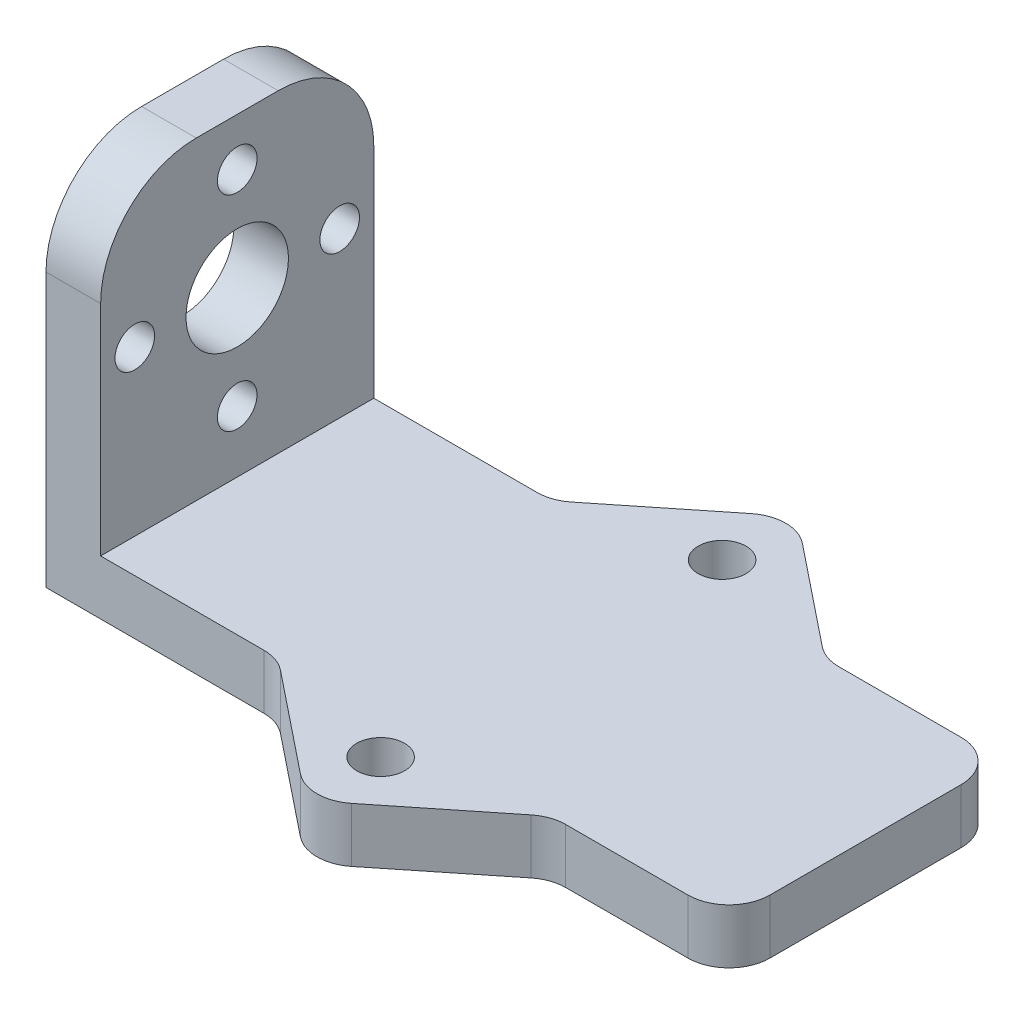
SolidWorks part; units mm, degrees
ref_plane "Front Plane" through (0, 0, 0) normal (0, 0, 1) x (1, 0, 0)
ref_plane "Top Plane" through (0, 0, 0) normal (0, 1, 0) x (1, 0, 0)
ref_plane "Right Plane" through (0, 0, 0) normal (1, 0, 0) x (0, 0, -1)
sketch "Sketch1" plane through (0, 0, 0) normal (0, 0, 1) x (1, 0, 0)
  line L0 (-23, 23) -> (-23, 0)
  line L1 (-23, 0) -> (23, 0)
  line L2 (23, 0) -> (23, -4)
  line L3 (23, -4) -> (-27, -4)
  line L4 (-27, -4) -> (-27, 23)
  line L5 (-27, 23) -> (-23, 23)
  point P2 (0, 0)
  dimension "D1" = 50
  dimension "D2" = 27
  dimension "D3" = 4
extrude "Boss-Extrude1" add sketch "Sketch1" along normal mid plane 20
fillet "Fillet1" radius 7 2 edges at (-25, 23, -10) (-25, 23, 10)
fillet "Fillet2" radius 3 2 edges at (23, -2, -10) (23, -2, 10)
sketch "Sketch2" plane through (-23, 0, 0) normal (1, 0, 0) x (0, 0, -1)
  line L1 (-10, 12) -> (10, 12) construction
  line L2 (-10, 0) -> (-10, 16) construction
  line L3 (10, 0) -> (10, 16) construction
  line L4 (-10, 0) -> (10, 0) construction
  circle A0 centre (0, 12) radius 7.5 construction
  circle A1 centre (0, 19.5) radius 1.45
  circle A2 centre (7.5, 12) radius 1.45
  circle A3 centre (0, 4.5) radius 1.45
  circle A4 centre (-7.5, 12) radius 1.45
  circle A5 centre (0, 12) radius 3.75
  point P10 (0, 12)
  dimension "D1" = 15
  dimension "D2" = 2.9
  dimension "D4" = 7.5
  dimension "D3" = 12
extrude "Cut-Extrude1" cut sketch "Sketch2" against normal mid plane 30
sketch "Sketch3" plane through (0, 0, 0) normal (0, 1, 0) x (1, 0, 0)
  line L0 (-10, 10) -> (0, 18)
  line L1 (20, 10) -> (-23, 10) construction
  line L2 (0, 18) -> (10, 10)
  line L3 (10, 10) -> (-10, 10)
  line L4 (0, 0) -> (7.5276, 0) construction
  line L5 (10, -10) -> (-10, -10)
  line L6 (0, -18) -> (10, -10)
  line L7 (-10, -10) -> (0, -18)
  dimension "D1" = 8
  dimension "D2" = 20
extrude "Boss-Extrude2" add sketch "Sketch3" against normal up to surface (4 mm away) up to face at (5.5404, -4, 0)
fillet "Fillet3" radius 3 6 edges at (10, -2, 10) (0, -2, 18) (-10, -2, 10) (0, -2, -18) (10, -2, -10) (-10, -2, -10)
sketch "Sketch4" plane through (0, 0, 0) normal (0, 1, 0) x (1, 0, 0)
  line L0 (0, -12.5) -> (0, 12.5) construction
  circle A0 centre (0, 12.5) radius 1.75
  circle A1 centre (0, -12.5) radius 1.75
  point P4 (0, 0)
  dimension "D1" = 3.5
  dimension "D2" = 25
extrude "Cut-Extrude2" cut sketch "Sketch4" against normal through all
